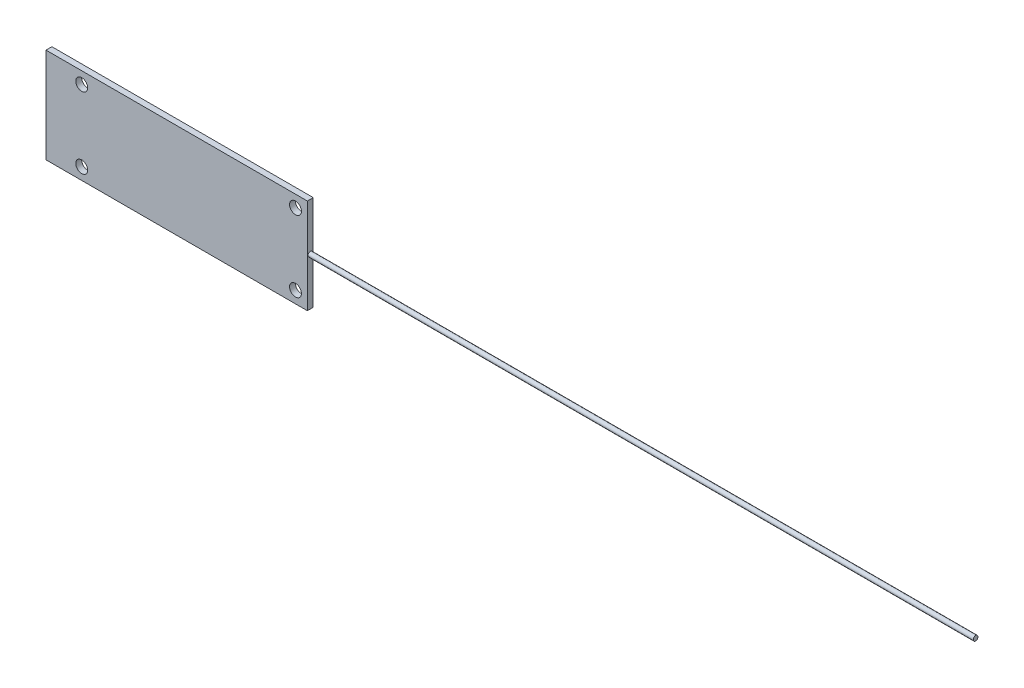
SolidWorks part; units mm, degrees
material "Printed Circuit Board"
ref_plane "Front Plane" through (0, 0, 0) normal (0, 0, 1) x (1, 0, 0)
ref_plane "Top Plane" through (0, 0, 0) normal (0, 1, 0) x (1, 0, 0)
ref_plane "Right Plane" through (0, 0, 0) normal (1, 0, 0) x (0, 0, -1)
sketch "Sketch1" plane through (0, 0, 0) normal (0, 0, 1) x (1, 0, 0)
  line L1 (-34.925, -12.7) -> (34.925, -12.7)
  line L2 (-34.925, -12.7) -> (-34.925, 12.7)
  line L3 (-34.925, 12.7) -> (34.925, 12.7)
  line L4 (34.925, -12.7) -> (34.925, 12.7)
  line L5 (-34.925, -12.7) -> (34.925, 12.7) construction
  line L6 (-34.925, 12.7) -> (34.925, -12.7) construction
  point P0 (0, 0)
  dimension "D1" = 69.85
  dimension "D2" = 25.4
extrude "Extrude1" add sketch "Sketch1" along normal blind 1.5748
sketch "Sketch2" plane through (0, 0, 1.5748) normal (0, 0, 1) x (1, 0, 0)
  line L0 (-34.925, 9.525) -> (-25.3822, 9.525) construction
  line L1 (-34.925, 12.7) -> (-34.925, -12.7) construction
  line L2 (-25.3822, 9.525) -> (31.75, 9.525) construction
  dimension "D1" = 9.5428
  dimension "D2" = 66.675
  dimension "D3" = 3.175
hole_wizard "1/8 (0.125) Diameter Hole1" positions "3DSketch1" profile "Sketch3" hole size "1/8" standard "Ansi Inch"
sketch3d "3DSketch1"
  point P0 (-25.3822, 9.525, 1.5748)
  point P3 (31.75, 9.525, 1.5748)
sketch "Sketch3" plane through (-25.3822, 9.525, 1.5748) normal (1, 0, 0) x (0, -1, 0)
  line L0 (0, 0) -> (0, 16.9559)
  line L1 (0, 16.9559) -> (1.5875, 16.002)
  line L2 (1.5875, 16.002) -> (1.5875, 0)
  line L5 (1.5875, 0) -> (0, 0)
  line L10 (0, 16.9559) -> (-1.5875, 16.002) construction
  line L11 (0, -6.35) -> (0, 107.95) construction
  dimension "Hole Dia." = 3.175
  dimension "Hole Depth" = 16.002
  dimension "Drill Angle" = 118
mirror "Mirror1" about plane through (0, 0, 0) normal (0, 1, 0) of "1/8 (0.125) Diameter Hole1"
sketch "Sketch4" plane through (34.925, 0, 0) normal (1, 0, 0) x (0, 0, -1)
  line L0 (0, 0) -> (-1.5441, 0) construction
  line L1 (0, -12.7) -> (0, 12.7) construction
  circle A0 centre (-0.772, 0) radius 0.635
  dimension "D1" = 1.27
extrude "Boss-Extrude1" add sketch "Sketch4" along normal blind 177.8
